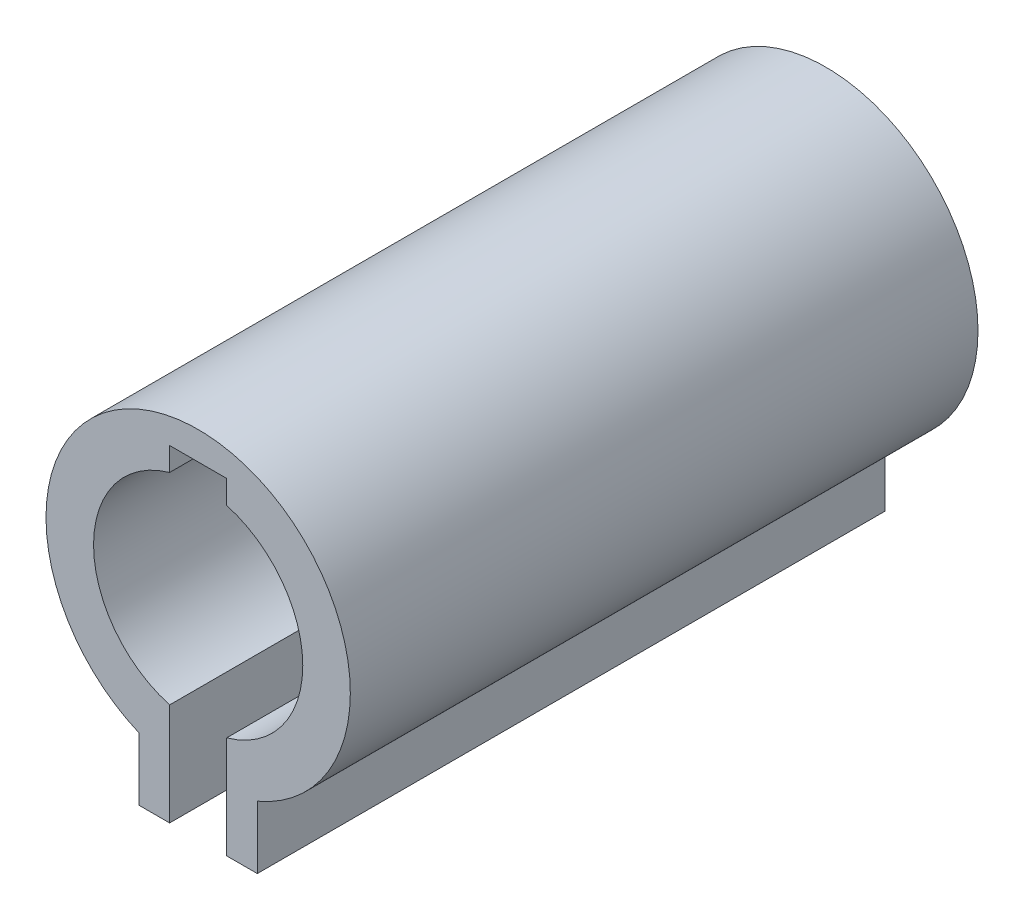
SolidWorks part; units mm, degrees
ref_plane "Front Plane" through (0, 0, 0) normal (0, 0, 1) x (1, 0, 0)
ref_plane "Top Plane" through (0, 0, 0) normal (0, 1, 0) x (1, 0, 0)
ref_plane "Right Plane" through (0, 0, 0) normal (1, 0, 0) x (0, 0, -1)
sketch "Sketch1" plane through (0, 0, 0) normal (0, 0, 1) x (1, 0, 0)
  circle A0 centre (0, 0) radius 11
  circle A1 centre (0, 0) radius 16
  dimension "D1" = 22
  dimension "D2" = 5
extrude "Boss-Extrude1" add sketch "Sketch1" along normal blind 33 and the other way blind 33
sketch "Sketch2" plane through (0, 0, 33) normal (0, 0, 1) x (1, 0, 0)
  line L0 (-3, 10.5402) -> (-3, 13.0402)
  line L2 (3, 13.0402) -> (3, 10.5402)
  line L3 (0, 0) -> (0, 13.0402) construction
  line L4 (-3, 13.0402) -> (0, 13.0402)
  line L5 (0, 13.0402) -> (3, 13.0402)
  line L6 (0, 0) -> (-3, 10.5402) construction
  line L7 (0, 0) -> (3, 10.5402) construction
  arc A0 (-3, 10.5402) -> (3, 10.5402) centre (0, 0) cw
  dimension "D1" = 3
  dimension "D2" = 3
  dimension "D3" = 2.5
extrude "Cut-Extrude1" cut sketch "Sketch2" against normal blind 33
mirror "Mirror2" about plane through (0, 0, 0) normal (0, 0, -1) of "Cut-Extrude1"
sketch "Sketch3" plane through (0, 0, 33) normal (0, 0, 1) x (1, 0, 0)
  line L0 (-3, -10.583) -> (-3, -15.7162)
  line L1 (-3, -15.7162) -> (-3, -10.583)
  line L2 (3, -10.583) -> (3, -15.7162)
  line L3 (-3, -10.583) -> (3, -10.583)
  line L4 (-3, -15.7162) -> (-3, -21.3357)
  line L5 (-3, -21.3357) -> (-6.2184, -21.3357)
  line L6 (-6.2184, -21.3357) -> (-6.2184, -14.7422)
  line L7 (-6.2184, -14.7422) -> (-3, -14.7422)
  line L8 (3, -15.7162) -> (3, -21.3357)
  line L9 (3, -21.3357) -> (6.2184, -21.3357)
  line L10 (6.2184, -21.3357) -> (6.2184, -14.7422)
  line L11 (6.2184, -14.7422) -> (3, -14.7422)
  arc A0 (-3, 10.583) -> (3, 10.583) centre (0, 0) ccw construction
  circle A1 centre (0, 0) radius 16 construction
  circle M6 centre (0, 0) radius 16
extrude "Boss-Extrude2" add sketch "Sketch3" against normal through all contours L6 L5 L4 M6 | L9 L10 L8 M6 region at (-4.6523, -18.3067, 33) region at (4.6523, -18.3067, 33)
sketch "Sketch4" plane through (0, 0, 33) normal (0, 0, 1) x (1, 0, 0)
  line L0 (-3, -10.583) -> (-3, -16.2715)
  line L1 (-3, -10.583) -> (3, -10.583)
  line L2 (3, -10.583) -> (3, -15.7162)
  line L3 (-3, -15.7162) -> (-3, -21.3357) construction
  line L4 (-3, -16.2715) -> (3, -16.2715)
  line L5 (3, -15.7162) -> (3, -21.3357) construction
  line L6 (3, -16.2715) -> (3, -15.7162)
  arc A0 (-3, 10.583) -> (3, 10.583) centre (0, 0) ccw construction
extrude "Cut-Extrude4" cut sketch "Sketch4" against normal through all
